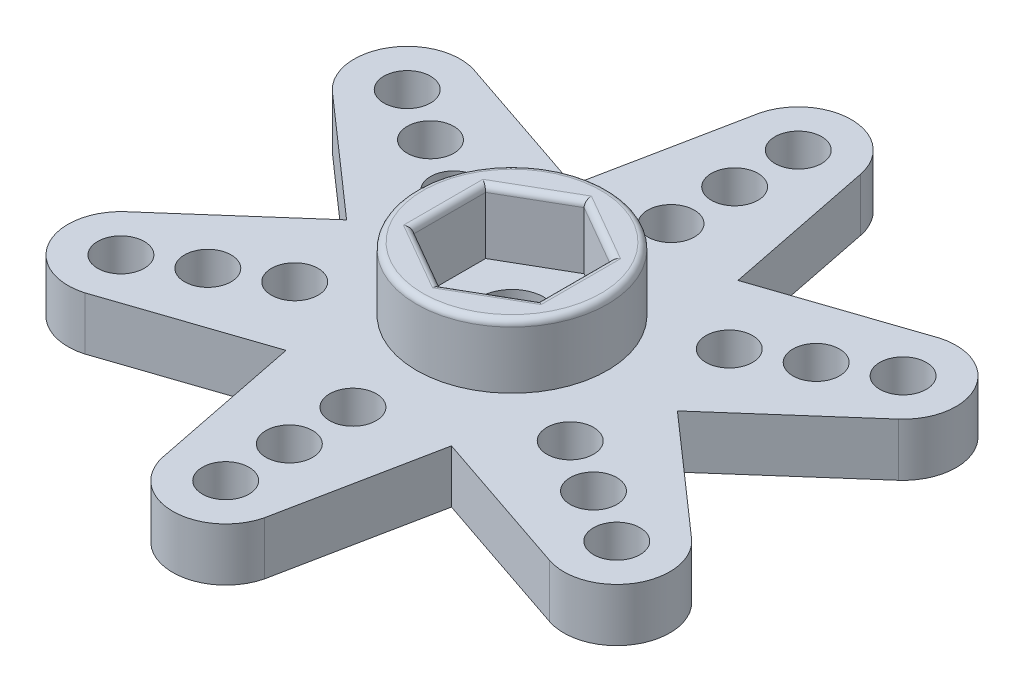
SolidWorks part; units mm, degrees
ref_plane "Alzado" through (0, 0, 0) normal (0, 0, 1) x (1, 0, 0)
ref_plane "Planta" through (0, 0, 0) normal (0, 1, 0) x (1, 0, 0)
ref_plane "Vista lateral" through (0, 0, 0) normal (1, 0, 0) x (0, 0, -1)
sketch "Croquis1" plane through (0, 0, 0) normal (0, 1, 0) x (1, 0, 0)
  line L0 (3.9, -6.755) -> (-3.9, -6.755) construction
  line L1 (0, 0) -> (0, -16) construction
  line L2 (-3.9, -6.755) -> (-10.9949, -9.151)
  line L3 (-13.342, -4.8725) -> (-7.8, 0)
  line L4 (-7.8, 0) -> (-13.4225, 4.9463)
  line L5 (-10.8907, 9.1183) -> (-3.9, 6.755)
  line L6 (-3.9, 6.755) -> (-2.4276, 14.0973)
  line L7 (2.4514, 13.9908) -> (3.9, 6.755)
  line L8 (3.9, 6.755) -> (10.9949, 9.151)
  line L9 (13.342, 4.8725) -> (7.8, 0)
  line L10 (3.9, -6.755) -> (2.4276, -14.0973)
  line L11 (7.8, 0) -> (13.4225, -4.9463)
  line L12 (-2.4514, -13.9908) -> (-3.9, -6.755)
  line L13 (10.8907, -9.1183) -> (3.9, -6.755)
  arc A0 (-13.342, -4.8725) -> (-10.9949, -9.151) centre (-11.6913, -6.75) ccw
  arc A1 (-10.8907, 9.1183) -> (-13.4225, 4.9463) centre (-11.6913, 6.75) ccw
  arc A2 (2.4514, 13.9908) -> (-2.4276, 14.0973) centre (0, 13.5) ccw
  arc A3 (13.342, 4.8725) -> (10.9949, 9.151) centre (11.6913, 6.75) ccw
  arc A4 (-2.4514, -13.9908) -> (2.4276, -14.0973) centre (0, -13.5) ccw
  arc A5 (10.8907, -9.1183) -> (13.4225, -4.9463) centre (11.6913, -6.75) ccw
  circle A6 centre (0, 0) radius 16 construction
  circle A8 centre (0, 0) radius 7.8 construction
  point P35 (0, 0)
  point P37 (0, 0)
  dimension "D1" = 32
  dimension "D5" = 5
  dimension "D2" = 15.6
extrude "Saliente-Extruir1" add sketch "Croquis1" along normal blind 2.5
sketch "Croquis2" plane through (0, 2.5, 0) normal (0, 1, 0) x (1, 0, 0)
  line L1 (0, -3.4) -> (2.9445, -1.7)
  line L2 (2.9445, -1.7) -> (2.9445, 1.7)
  line L3 (2.9445, 1.7) -> (0, 3.4)
  line L4 (0, 3.4) -> (-2.9445, 1.7)
  line L5 (-2.9445, 1.7) -> (-2.9445, -1.7)
  line L6 (-2.9445, -1.7) -> (0, -3.4)
  circle A0 centre (0, 0) radius 4.5
  circle A1 centre (0, 0) radius 3.4 construction
  circle A2 centre (0, 0) radius 2.9445 construction
  dimension "D1" = 9
  dimension "D2" = 6.8
extrude "Saliente-Extruir2" add sketch "Croquis2" along normal blind 3
sketch "Croquis3" plane through (0, 0, 0) normal (0, -1, 0) x (1, 0, 0)
  circle A0 centre (0, 0) radius 1.5
  dimension "D1" = 3
extrude "Cortar-Extruir1" cut sketch "Croquis3" against normal up to next
sketch "Croquis4" plane through (0, 0, 0) normal (0, -1, 0) x (1, 0, 0)
  circle A0 centre (0, 0) radius 2.8
  dimension "D1" = 5.6
extrude "Cortar-Extruir2" cut sketch "Croquis4" against normal offset from surface (1 mm away) 1.5 up to face at (0, 2.5, 1.5)
sketch "Croquis5" plane through (0, 0, 0) normal (0, -1, 0) x (1, 0, 0)
  circle A0 centre (0, 0) radius 4.5
  circle A1 centre (0, 0) radius 3.5
  dimension "D1" = 9
  dimension "D2" = 7
extrude "Cortar-Extruir3" cut sketch "Croquis5" against normal blind 0.5
fillet "Redondeo1" radius 0.3 10 edges at (0, 0, -4.5) (0, 0, -2.8) (0, 0, -3.5) (0, 5.5, 4.5) (2.9445, 5.5, 0) (1.4722, 5.5, 2.55) (-1.4722, 5.5, 2.55) (-2.9445, 5.5, 0) (-1.4722, 5.5, -2.55) (1.4722, 5.5, -2.55)
sketch "Croquis6" plane through (0, 0, 0) normal (0, -1, 0) x (1, 0, 0)
  line L0 (0, 0) -> (0, -16.5) construction
  circle A0 centre (0, 0) radius 10.5 construction
  circle A1 centre (0, 0) radius 13.5 construction
  circle A3 centre (0, 0) radius 7.5 construction
  circle A5 centre (0, -13.5) radius 1.1
  circle A6 centre (0, -10.5) radius 1.1
  circle A7 centre (0, -7.5) radius 1.1
  dimension "D2" = 27
  dimension "D3" = 21
  dimension "D4" = 15
extrude "Cortar-Extruir4" cut sketch "Croquis6" against normal up to next
pattern_circular "MatrizC1" count 6 over 360 about axis through (0, 1, 0) along (0, -1, 0) of "Cortar-Extruir4"
